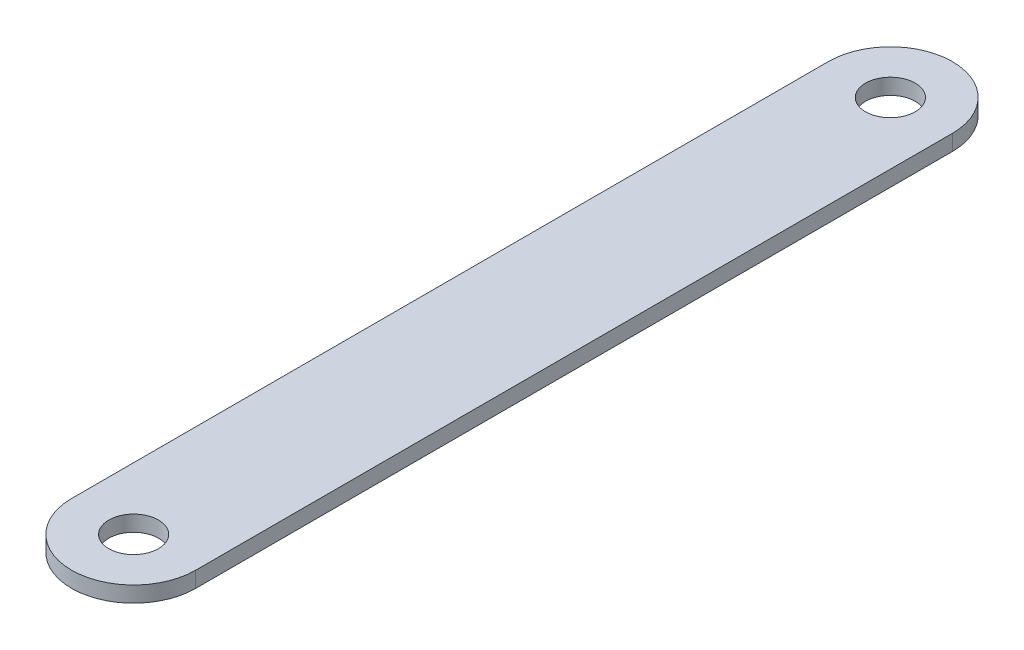
SolidWorks part; units mm, degrees
ref_plane "Front Plane" through (0, 0, 0) normal (0, 0, 1) x (1, 0, 0)
ref_plane "Top Plane" through (0, 0, 0) normal (0, 1, 0) x (1, 0, 0)
ref_plane "Right Plane" through (0, 0, 0) normal (1, 0, 0) x (0, 0, -1)
sketch "Sketch2" plane through (0, 0, 0) normal (0, 1, 0) x (1, 0, 0)
  line L0 (-5, 60.9469) -> (-5, 0)
  line L1 (5, 60.9469) -> (5, 0)
  circle A0 centre (0, 0) radius 2
  circle A1 centre (0, 60.9469) radius 2
  arc A2 (5, 0) -> (-5, 0) centre (0, 0) cw
  arc A3 (5, 60.9469) -> (-5, 60.9469) centre (0, 60.9469) ccw
  point P7 (43.1243, 0)
  dimension "D2" = 4
  dimension "D3" = 5
  dimension "D1" = 60.9469
extrude "Boss-Extrude1" add sketch "Sketch2" along normal blind 1.27
